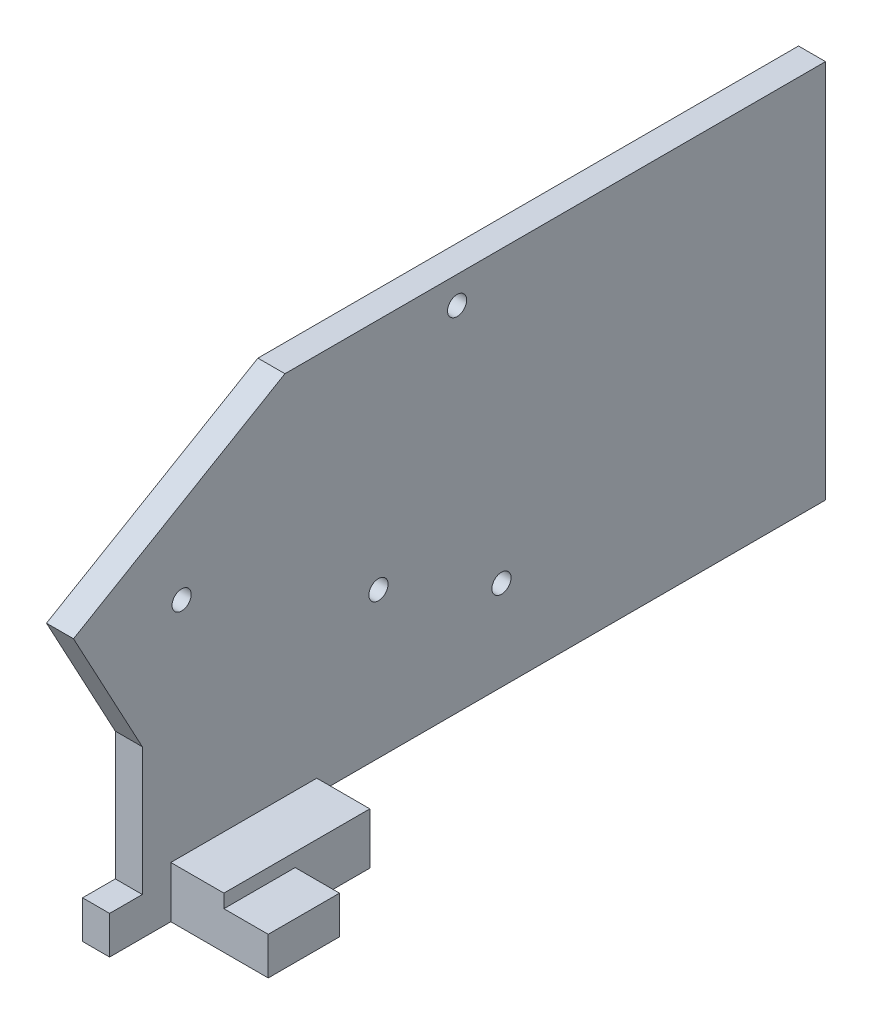
SolidWorks part; units mm, degrees
material "BRASS"
ref_plane "Front Plane" through (0, 0, 0) normal (0, 0, 1) x (1, 0, 0)
ref_plane "Top Plane" through (0, 0, 0) normal (0, 1, 0) x (1, 0, 0)
ref_plane "Right Plane" through (0, 0, 0) normal (1, 0, 0) x (0, 0, -1)
sketch "Sketch2" plane through (0, 0, 0) normal (1, 0, 0) x (0, 0, -1)
  line L6 (0, 0) -> (76.2, 0)
  line L7 (76.2, 0) -> (176.67, 0)
  line L10 (49.67, 89.2048) -> (0, 60.1162)
  line L12 (49.67, 89.2048) -> (176.67, 89.2048)
  line L13 (176.67, 89.2048) -> (176.67, 0)
  line L15 (0, 60.1162) -> (0, 0)
  line L16 (22.86, 0) -> (22.86, 3.175)
  line L17 (57.15, 0) -> (57.15, 3.175)
  line L18 (44.45, 0) -> (44.45, 3.175) construction
  line L19 (31.75, 0) -> (31.75, 3.175) construction
  line L20 (22.86, 3.175) -> (57.15, 3.175)
  line L21 (57.15, 0) -> (57.15, -8.89)
  line L22 (57.15, -8.89) -> (8.4806, -8.89)
  line L23 (0, 60.1162) -> (16.1709, 30.0581)
  line L24 (8.4806, -8.89) -> (8.4806, 0)
  line L25 (22.86, 0) -> (22.86, -8.89)
  line L26 (25.4, 55.3212) -> (71.6421, 34.29) construction
  line L27 (71.6421, 34.29) -> (100.5434, 21.1455) construction
  line L28 (16.1709, 30.0581) -> (16.1709, 0)
  circle A0 centre (25.4, 55.3212) radius 2.2479
  circle A1 centre (90.1192, 82.8548) radius 2.2479
  circle A3 centre (25.4, 55.3212) radius 50.8 construction
  circle A4 centre (71.6421, 34.29) radius 31.75 construction
  circle A5 centre (71.6421, 34.29) radius 2.2479
  circle A6 centre (100.5434, 21.1455) radius 2.2479
  point P30 (71.6421, 34.29)
  dimension "D3" = 4.4958
  dimension "D14" = 101.6
  dimension "D16" = 63.5
  dimension "D17" = 4.4958
  dimension "D1" = 76.2
  dimension "D2" = 25.4
  dimension "D4" = 55.3212
  dimension "D5" = 82.8548
  dimension "D6" = 70.3326
  dimension "D7" = 40.4492
  dimension "D8" = 6.35
  dimension "D9" = 3.175
  dimension "D10" = 12.7
  dimension "D11" = 19.05
  dimension "D12" = 8.89
  dimension "D13" = 12.7
  dimension "D15" = 34.29
  dimension "D18" = 8.89
  dimension "D19" = 127
extrude "Boss-Extrude3" add sketch "Sketch2" against normal blind 6.35 contours L20 L16 L6 L17 | L16 L20 L17 L6 L7 L13 L12 L10 L15 A1 A0 | L6 L25 L22 L21 | L25 L6 L24 L22 region at (0, -4.445, -15.6703) region at (0, 44.2274, -96.6346) region at (0, 1.5875, -40.005) region at (0, -4.445, -40.005)
extrude "Boss-Extrude4" add sketch "Sketch2<5>" along normal blind 12.4714 contours L20 L16 L6 L17 | L6 L25 L22 L21 region at (0, 1.5875, -40.005) region at (0, -4.445, -40.005)
sketch "Sketch2<5>" plane through (0, 0, 0) normal (1, 0, 0) x (0, 0, -1) same geometry as "Sketch2"
sketch "Sketch3" plane through (12.4714, 0, 0) normal (1, 0, 0) x (0, 0, -1)
  line L0 (39.6, 0) -> (39.6, -8.89)
  line L1 (57.15, -8.89) -> (22.86, -8.89) construction
  line L2 (39.6, 0) -> (39.6, -7.4092) construction
  line L3 (39.6, -8.89) -> (22.86, -8.89)
  line L4 (22.86, -8.89) -> (22.86, 0)
  line L5 (22.86, -8.89) -> (22.86, 3.175) construction
  line L6 (22.86, 0) -> (39.6, 0)
extrude "Boss-Extrude5" add sketch "Sketch3" along normal blind 10.414
